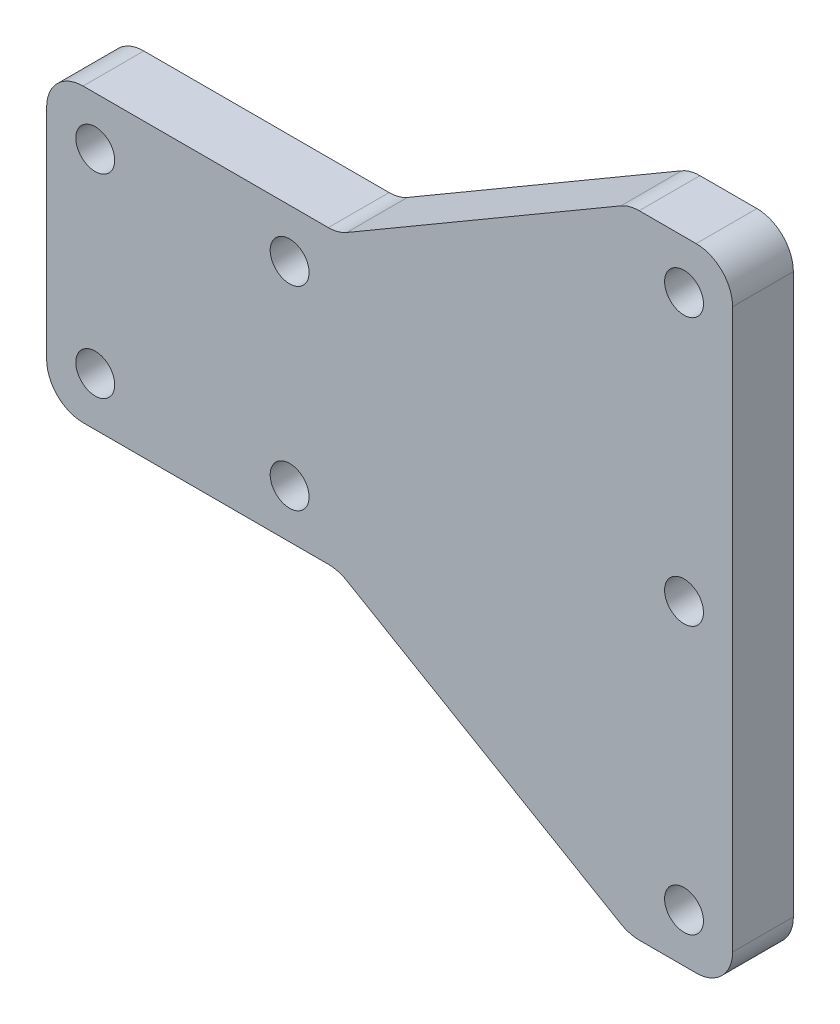
SolidWorks part; units mm, degrees
material "ABS"
ref_plane "前视基准面" through (0, 0, 0) normal (0, 0, 1) x (1, 0, 0)
ref_plane "上视基准面" through (0, 0, 0) normal (0, 1, 0) x (1, 0, 0)
ref_plane "右视基准面" through (0, 0, 0) normal (1, 0, 0) x (0, 0, -1)
sketch "草图1" plane through (0, 0, 0) normal (0, 0, 1) x (1, 0, 0)
  line L0 (0, 0) -> (-67.3124, 0) construction
  line L1 (134.6248, 0) -> (-67.3124, 116.5885)
  line L2 (-67.3124, 116.5885) -> (-67.3124, -116.5885)
  line L3 (-67.3124, -116.5885) -> (134.6248, 0)
  line L4 (-67.3124, 116.5885) -> (-67.3124, 85.5885) construction
  line L5 (-67.3124, 85.5885) -> (-67.3124, 30) construction
  line L6 (0, 0) -> (117.3042, 0) construction
  line L7 (117.3042, 10) -> (117.3042, -10)
  line L8 (-49.9919, -106.5885) -> (-67.3124, -96.5885)
  line L9 (-58.6521, -101.5885) -> (-67.3124, -116.5885) construction
  line L10 (0, 0) -> (-58.6521, -101.5885) construction
  line L11 (-67.3124, 96.5885) -> (-49.9919, 106.5885)
  line L12 (85.9645, 5) -> (-38.6521, 76.9474)
  line L13 (-47.3124, 71.9474) -> (-47.3124, -71.9474)
  line L14 (-38.6521, -76.9474) -> (85.9645, -5)
  line L15 (85.9645, 5) -> (85.9645, -5)
  line L16 (-38.6521, -76.9474) -> (-47.3124, -71.9474)
  line L17 (-47.3124, 71.9474) -> (-38.6521, 76.9474)
  line L18 (94.6248, 0) -> (-47.3124, 81.9474) construction
  line L19 (-47.3124, 81.9474) -> (-47.3124, -81.9474) construction
  line L20 (-47.3124, -81.9474) -> (94.6248, 0) construction
  line L24 (117.3042, 0) -> (134.6248, 0) construction
  line L25 (-58.6521, 101.5885) -> (-67.3124, 116.5885) construction
  line L26 (2.8479, -52.9874) -> (-47.3124, -24.0274)
  line L27 (60.9645, -25.5) -> (60.9645, 25.5) construction
  line L28 (60.9645, 0) -> (40.4645, 0) construction
  line L29 (81.4645, 4.5) -> (81.4645, 7.5981)
  line L30 (81.4645, -4.5) -> (81.4645, -7.5981)
  line L31 (-52.5659, -40.0468) -> (-8.3986, -65.5468) construction
  line L32 (44.4645, 28.96) -> (44.4645, -28.96)
  line L33 (-36.8351, -72.8003) -> (-34.1521, -74.3494)
  line L34 (-44.6294, -68.3003) -> (-47.3124, -66.7513)
  line L35 (0, 0) -> (-58.6521, 101.5885) construction
  line L36 (-47.3124, 24.0274) -> (2.8479, 52.9874)
  line L37 (-8.3986, 65.5468) -> (-52.5659, 40.0468) construction
  line L38 (-44.6294, 68.3003) -> (-47.3124, 66.7513)
  line L39 (-36.8351, 72.8003) -> (-34.1521, 74.3494)
  line L40 (-47.3124, 24.0274) -> (-59.3124, 25.5)
  line L41 (40.4645, 22) -> (40.4645, -22) construction
  line L42 (-47.3124, 16) -> (-59.3124, 0)
  line L43 (-67.3124, 25.5) -> (-47.3124, 25.5) construction
  line L44 (-67.3124, 34.5) -> (-59.3124, 34.5)
  line L45 (-59.3124, 34.5) -> (-59.3124, 25.5)
  line L46 (-59.3124, 25.5) -> (-67.3124, 25.5)
  line L47 (-59.3124, 25.5) -> (-59.3124, -25.5)
  line L48 (-59.3124, -34.5) -> (-59.3124, -25.5)
  line L49 (-59.3124, -25.5) -> (-67.3124, -25.5)
  line L50 (-67.3124, -34.5) -> (-59.3124, -34.5)
  line L51 (-52.5659, 40.0468) -> (-52.5659, 18.0468) construction
  line L52 (-52.5659, -40.0468) -> (-52.5659, -18.0468) construction
  line L53 (60.9645, 25.5) -> (41.9119, 36.5) construction
  line L54 (63.5341, 41.0442) -> (59.5341, 34.116)
  line L55 (-47.3124, -16) -> (-59.3124, 0)
  line L56 (-59.3124, -25.5) -> (-47.3124, -24.0274)
  line L57 (51.7398, 38.616) -> (55.7398, 45.5442)
  line L58 (51.7398, 38.616) -> (7.5725, 64.116)
  line L59 (59.5341, 34.116) -> (51.7398, 38.616)
  line L60 (3.7783, 75.5442) -> (-0.2217, 68.616)
  line L61 (-0.2217, 68.616) -> (7.5725, 64.116)
  line L62 (7.5725, 64.116) -> (11.5725, 71.0442)
  line L63 (7.5725, 64.116) -> (2.8479, 52.9874)
  line L64 (9.7998, 48.9737) -> (29.6562, 51.366)
  line L68 (37.5126, 32.9737) -> (29.6562, 51.366)
  line L69 (-1.1797, -46.0433) -> (-39.2848, -24.0433) construction
  line L70 (44.4645, 28.96) -> (51.7398, 38.616)
  line L71 (-8.3986, -65.5468) -> (10.654, -54.5468) construction
  line L72 (3.7783, -75.5442) -> (-0.2217, -68.616)
  line L73 (7.5725, -64.116) -> (11.5725, -71.0442)
  line L74 (7.5725, -64.116) -> (51.7398, -38.616)
  line L75 (-0.2217, -68.616) -> (7.5725, -64.116)
  line L76 (63.5341, -41.0442) -> (59.5341, -34.116)
  line L77 (59.5341, -34.116) -> (51.7398, -38.616)
  line L78 (51.7398, -38.616) -> (55.7398, -45.5442)
  line L79 (51.7398, -38.616) -> (44.4645, -28.96)
  line L80 (37.5126, -32.9737) -> (29.6562, -51.366)
  line L84 (9.7998, -48.9737) -> (29.6562, -51.366)
  line L85 (-39.2848, 24.0433) -> (-1.1797, 46.0433) construction
  line L86 (2.8479, -52.9874) -> (7.5725, -64.116)
  line L87 (-12, 12) -> (-12, -12)
  line L88 (-8, -8) -> (8, -8)
  line L89 (-43.963, 16.1462) -> (7.9985, 46.1462)
  line L90 (35.9645, 30) -> (35.9645, -30)
  line L91 (7.9985, -46.1462) -> (-43.963, -16.1462)
  line L92 (-43.963, 16.1462) -> (-43.963, -16.1462)
  line L93 (7.9985, -46.1462) -> (35.9645, -30)
  line L94 (7.9985, 46.1462) -> (35.9645, 30)
  line L98 (-8, -8) -> (-8, 8)
  line L99 (-8, 8) -> (8, 8)
  line L100 (8, -8) -> (8, 8)
  line L101 (-8, -8) -> (8, 8) construction
  line L102 (-8, 8) -> (8, -8) construction
  line L103 (-12, -12) -> (12, -12)
  line L104 (12, -12) -> (12, 12)
  line L105 (12, 12) -> (-12, 12)
  line L109 (44.4645, 26) -> (35.9645, 26)
  line L110 (35.9645, 26) -> (12, 12)
  line L111 (44.4645, -26) -> (35.9645, -26)
  line L112 (12, -12) -> (35.9645, -26)
  line L161 (0, 0) -> (-58.6521, -101.5885) construction
  line L162 (0, 0) -> (-58.6521, 101.5885) construction
  circle A0 centre (0, 0) radius 67.3124 construction
  circle A1 centre (-59.9021, 103.7535) radius 2.5
  circle A2 centre (-59.9021, 103.7535) radius 10.3078
  circle A3 centre (119.8042, 0) radius 10.3078
  circle A4 centre (119.8042, 0) radius 2.5
  circle A5 centre (-59.9021, -103.7535) radius 10.3078
  circle A6 centre (-59.9021, -103.7535) radius 2.5
  circle A7 centre (40.4645, 0) radius 1.6
  circle A8 centre (60.9645, 25.5) radius 1.6
  circle A9 centre (81.4645, 0) radius 1.6
  circle A10 centre (81.4645, 0) radius 4.5
  circle A11 centre (60.9645, -25.5) radius 1.6
  circle A22 centre (-20.2323, -35.0433) radius 1.6
  circle A23 centre (-52.5659, -40.0468) radius 1.6
  circle A24 centre (-8.3986, -65.5468) radius 1.6
  circle A25 centre (-40.7323, -70.5503) radius 4.5
  circle A26 centre (-40.7323, -70.5503) radius 1.6
  circle A27 centre (-20.2323, 35.0433) radius 1.6
  circle A28 centre (-8.3986, 65.5468) radius 1.6
  circle A29 centre (-52.5659, 40.0468) radius 1.6
  circle A30 centre (-40.7323, 70.5503) radius 4.5
  circle A31 centre (-40.7323, 70.5503) radius 1.6
  circle A32 centre (40.4645, -22) radius 1.6
  circle A33 centre (40.4645, 22) radius 1.6
  circle A34 centre (-52.5659, 18.0468) radius 1.6
  circle A35 centre (-52.5659, -18.0468) radius 1.6
  circle A36 centre (10.654, 54.5468) radius 1.6
  circle A37 centre (41.9119, 36.5) radius 1.6
  circle A38 centre (-1.1797, -46.0433) radius 1.6
  circle A39 centre (-39.2848, -24.0433) radius 1.6
  circle A40 centre (41.9119, -36.5) radius 1.6
  circle A41 centre (10.654, -54.5468) radius 1.6
  circle A42 centre (-39.2848, 24.0433) radius 1.6
  circle A43 centre (-1.1797, 46.0433) radius 1.6
  circle A44 centre (-8, 8) radius 1.6
  circle A45 centre (-8, -8) radius 1.6
  circle A46 centre (8, -8) radius 1.6
  circle A47 centre (8, 8) radius 1.6
  point P13 (117.3042, 0)
  point P21 (0, 0)
  point P26 (85.9645, 0)
  point P33 (0, 0)
  point P36 (0, 0)
  point P45 (0, 0)
  point P96 (0, 0)
  point P97 (-17.9823, 31.1462)
  point P98 (0, 0)
  point P104 (-59.3124, 0)
  point P116 (-43.963, 0)
  point P118 (0, 0)
  point P172 (0, 0)
  point P173 (0, 0)
  dimension "D9" = 5
  dimension "D10" = 20.6155
  dimension "D14" = 3.2
  dimension "D15" = 9
  dimension "D19" = 4.5
  dimension "D23" = 3.2
  dimension "D27" = 3.2
  dimension "D31" = 3.2
  dimension "D1" = 233.1769
  dimension "D2" = 31
  dimension "D4" = 20
  dimension "D7" = 10
  dimension "D5" = 3
  dimension "D12" = 25.5
  dimension "D13" = 20.5
  dimension "D16" = 4
  dimension "D17" = 3
  dimension "D20" = 9
  dimension "D21" = 8
  dimension "D22" = 60
  dimension "D24" = 22
  dimension "D28" = 16
  dimension "D29" = 3
  dimension "D30" = 16
  dimension "D33" = 30
  dimension "D18" = 4.5
  dimension "D25" = 22
  dimension "D32" = 4
  dimension "D34" = 4
  dimension "D35" = 4
  dimension "D36" = 4
  dimension "D37" = 4
  dimension "D38" = 23.9645
  dimension "D39" = 4
  dimension "D40" = 23.9645
  dimension "D6" = 20
  dimension "D8" = 3
  dimension "D11" = 3
  dimension "D26" = 3
ref_plane "基准面4" through (-67.3124, 0, 0) normal (1, 0, 0) x (0, 0, -1)
extrude "凸台-拉伸1" add sketch "草图1" along normal blind 5 contours A47 L99 A44 L98 A45 L88 A46 L100 | L104 L105 L87 L103 A47 L100 A46 L88 A45 L98 A44 L99 | L104 L112 L90 L110 | L111 L32 L109 L90 A7 A32 A33 region at (43.9376, 0, 0) region at (25.4538, 0, 0) region at (11.6606, 0, 0) region at (0, 0, 0)
fillet "圆角1" radius 3 8 edges at (44.4645, 26, 2.5) (44.4645, -26, 2.5) (35.9645, -26, 2.5) (35.9645, 26, 2.5) (12, 12, 2.5) (-12, 12, 2.5) (12, -12, 2.5) (-12, -12, 2.5)
